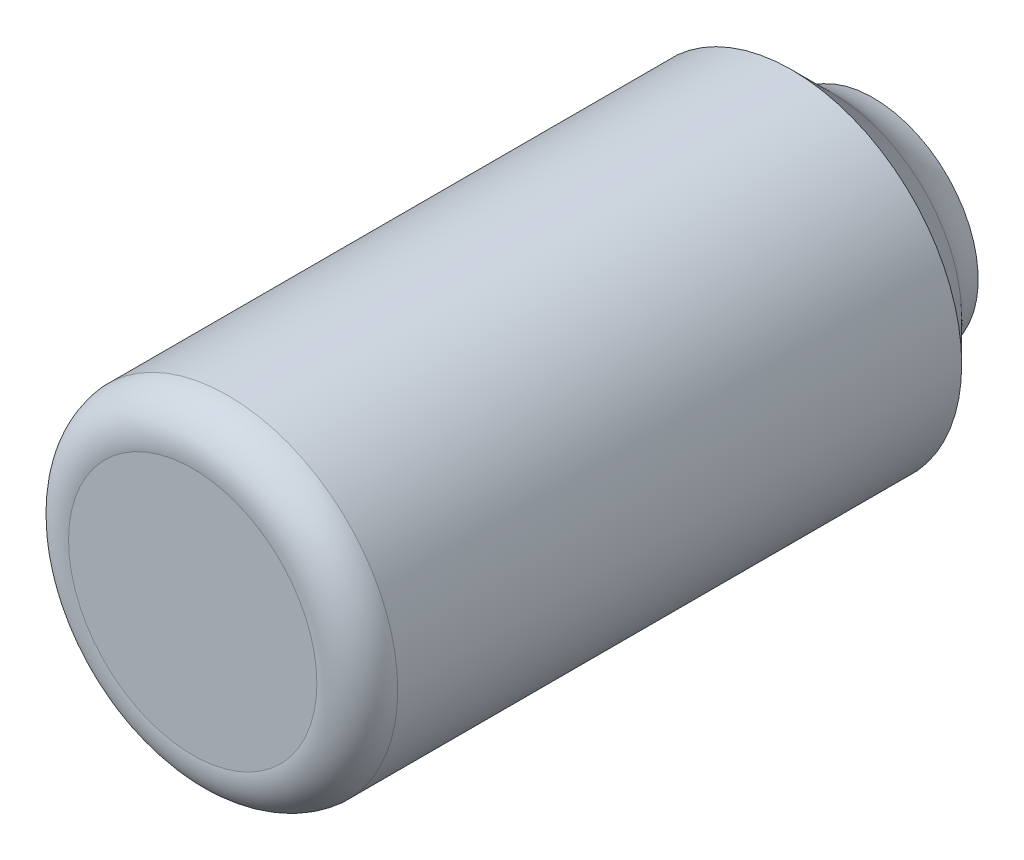
SolidWorks part; units mm, degrees
ref_plane "Front Plane" through (0, 0, 0) normal (0, 0, 1) x (1, 0, 0)
ref_plane "Top Plane" through (0, 0, 0) normal (0, 1, 0) x (1, 0, 0)
ref_plane "Right Plane" through (0, 0, 0) normal (1, 0, 0) x (0, 0, -1)
sketch "Sketch2" plane through (0, 0, 0) normal (0, 1, 0) x (1, 0, 0)
  line L0 (47.8355, 141.4492) -> (36.6804, 141.4492)
  line L1 (0, 0) -> (47.8355, 0) construction
  line L2 (0, 0) -> (0, 141.4492) construction
  line L3 (0, 141.4492) -> (47.8355, 141.4492) construction
  line L4 (47.8355, 0) -> (47.8355, 141.4492) construction
  line L5 (36.6804, 141.4492) -> (36.6804, 139.6953)
  line L6 (36.6804, 139.6953) -> (29.7546, 132.7695)
  line L7 (29.7546, 132.7695) -> (29.7546, 72.7687)
  line L8 (34.6242, 69.0347) -> (47.8355, 69.0347)
  line L9 (47.8355, 141.4492) -> (47.8355, 69.0347)
  arc A0 (29.7546, 72.7687) -> (34.6242, 69.0347) centre (34.0564, 73.3365) ccw
revolve "Revolve1" add sketch "Sketch2" angle 360 about L9
fillet "Fillet1" radius 10 1 edges at (36.6804, 0, -139.6953)
sketch "Sketch3" plane through (0, 0, -141.4492) normal (0, 0, -1) x (-1, 0, 0)
  circle A0 centre (-47.8355, 0) radius 10.6066
extrude "Cut-Extrude1" cut sketch "Sketch3" against normal blind 1
fillet "Fillet2" radius 1 1 edges at (37.2289, 0, -140.4492)
sketch "Sketch4" plane through (0, 0, -140.4492) normal (0, 0, -1) x (-1, 0, 0)
  line L0 (-53.2449, -2.5278) -> (-53.9307, -1.192)
  line L1 (-53.9307, -1.192) -> (-53.9307, 0)
  line L2 (-53.9307, 0) -> (-53.3971, 0.9867)
  line L3 (-53.3971, 0.9867) -> (-52.7269, 0.9867)
  line L4 (-52.7269, 0.9867) -> (-52.0042, 0.9867)
  line L5 (-52.0042, 0.9867) -> (-51.0286, 1.0909)
  line L6 (-51.0286, 1.0909) -> (-49.9756, 1.0909)
  line L7 (-49.9756, 1.0909) -> (-48.9587, 1.0909)
  line L8 (-48.9587, 1.0909) -> (-48.872, 1.2511)
  line L9 (-48.872, 1.2511) -> (-47.8198, 1.2511)
  line L10 (-47.8198, 1.2511) -> (-47.7469, 1.2117)
  line L11 (-47.7469, 1.2117) -> (-47.3738, 0.4849)
  line L12 (-47.3738, 0.4849) -> (-47.1661, -0.3441)
  line L13 (-47.1661, -0.3441) -> (-47.1661, -1.0872)
  line L14 (-47.1661, -1.0872) -> (-47.5603, -1.8162)
  line L15 (-47.5603, -1.8162) -> (-47.9451, -2.5278)
  line L16 (-47.9451, -2.5278) -> (-48.3758, -2.5278)
  line L17 (-48.3758, -2.5278) -> (-49.1104, -2.5278)
  line L18 (-49.1104, -2.5278) -> (-49.9756, -2.5278)
  line L19 (-49.9756, -2.5278) -> (-50.6766, -2.7034)
  line L20 (-50.6766, -2.7034) -> (-51.7545, -2.7034)
  line L21 (-51.7545, -2.7034) -> (-52.3415, -2.8504)
  line L22 (-52.3415, -2.8504) -> (-53.2449, -2.5278)
  point P10 (-53.2449, -2.5278)
  point P24 (-48.9587, 1.2511)
  point P25 (-52.0042, 0.9867)
  point P26 (0, 0)
extrude "Boss-Extrude1" add sketch "Sketch4" along normal blind 1
sketch "Sketch5" plane through (0, 0, -141.4492) normal (0, 0, -1) x (-1, 0, 0)
  circle A0 centre (-51.6153, -0.9698) radius 1.3575
extrude "Cut-Extrude2" cut sketch "Sketch5" against normal blind 1
